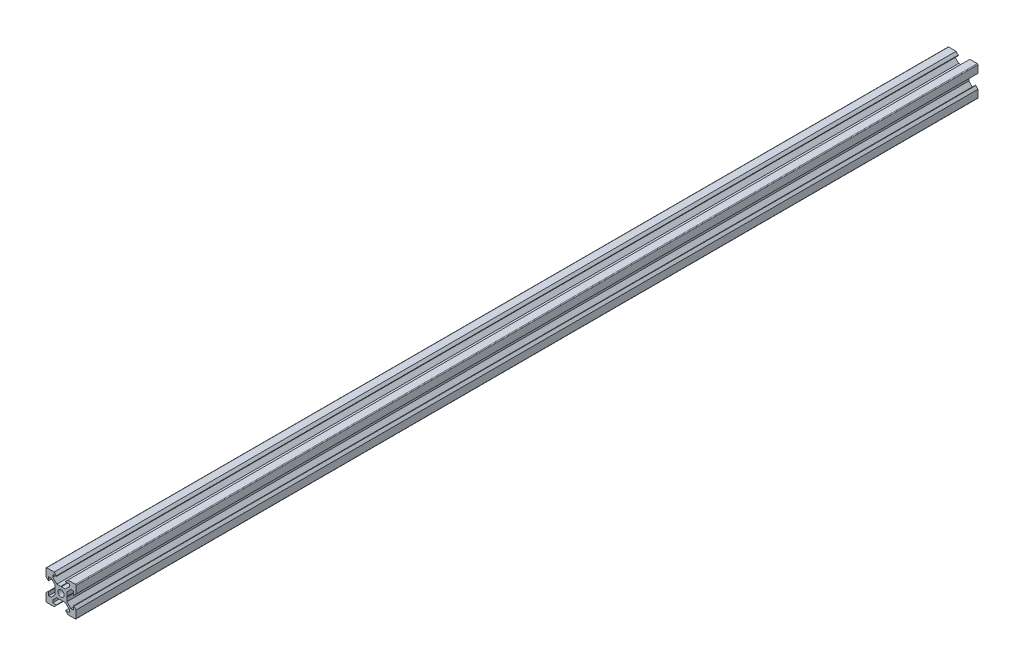
SolidWorks part; units mm, degrees
ref_plane "Plan de face" through (0, 0, 0) normal (0, 0, 1) x (1, 0, 0)
ref_plane "Plan de dessus" through (0, 0, 0) normal (0, 1, 0) x (1, 0, 0)
ref_plane "Plan de droite" through (0, 0, 0) normal (1, 0, 0) x (0, 0, -1)
ref_axis "Axe" through (0, 0, -13.782) along (0, 0, 1)
sketch "Esquisse1" plane through (0, 0, 0) normal (0, 0, 1) x (1, 0, 0)
  line L0 (0, 22.8977) -> (0, -22.8977) construction
  line L1 (-33.6074, 0) -> (33.6074, 0) construction
  line L2 (0, 0) -> (-22.2114, 22.2114) construction
  line L3 (-9.5, 10) -> (-4.58, 10)
  line L4 (-4.58, 10) -> (-3.125, 8.545)
  line L5 (-3.125, 8.545) -> (-3.125, 8.2)
  line L6 (-3.125, 8.2) -> (-5.5, 8.2)
  line L7 (-2.8393, 3.9) -> (-5.5, 6.5607)
  line L8 (-2.8393, 3.9) -> (-0.21, 3.9)
  line L9 (-5.5, 6.5607) -> (-5.5, 8.2)
  line L10 (0, 3.69) -> (0, 2.1)
  line L11 (-3.9, 2.8393) -> (-6.5607, 5.5)
  line L12 (-8.545, 3.125) -> (-8.2, 3.125)
  line L13 (-8.2, 3.125) -> (-8.2, 5.5)
  line L14 (-6.5607, 5.5) -> (-8.2, 5.5)
  line L15 (-10, 4.58) -> (-8.545, 3.125)
  line L16 (-10, 9.5) -> (-10, 4.58)
  line L17 (-0.21, 3.9) -> (0, 3.69)
  line L18 (-3.9, 2.8393) -> (-3.9, 0.21)
  line L19 (-3.69, 0) -> (-2.1, 0)
  line L20 (-3.9, 0.21) -> (-3.69, 0)
  arc A0 (-2.1, 0) -> (0, 2.1) centre (0, 0) cw
  arc A1 (-9.5, 10) -> (-10, 9.5) centre (-9.5, 9.5) ccw
  point P4 (0, 0)
  point P7 (0, 0)
  point P30 (-10, 10)
  dimension "D5" = 11
  dimension "D2" = 2.1
  dimension "D3" = 6.25
  dimension "D10" = 0.5
  dimension "D4" = 9.16
  dimension "D6" = 1.5
  dimension "D7" = 1.8
  dimension "D8" = 4.3
  dimension "D9" = 20
  dimension "D11" = 0.42
extrude "Boss.-Extru.1" add sketch "Esquisse1" along normal blind 600
sketch "Esquisse3" plane through (0, 0, 600) normal (0, 0, 1) x (1, 0, 0)
  line L0 (0, 0) -> (-9.8536, 9.8536) construction
  line L1 (-8.2, 8.2) -> (-8.2, 6.57)
  line L2 (-8.2, 6.57) -> (-7.54, 6.57)
  line L3 (-7.54, 6.57) -> (-6.57, 7.54)
  line L4 (-8.2, 3.125) -> (-8.2, 5.5) construction
  line L5 (-6.57, 8.2) -> (-6.57, 7.54)
  line L6 (-8.2, 8.2) -> (-6.57, 8.2)
  line L7 (-5.5, 6.5607) -> (-5.5, 8.2) construction
  arc A0 (-9.5, 10) -> (-10, 9.5) centre (-9.5, 9.5) ccw construction
  point P13 (-7.055, 7.055)
  point P14 (-6.57, 7.87)
  dimension "D1" = 1.07
extrude "Enlèv. mat.-Extru.1" [suppressed] cut sketch "Esquisse3" against normal through all
pattern_circular "Répétition circulaire1" count 4 every 90 about axis through (0, 0, -13.782) along (0, 0, 1) of "Boss.-Extru.1", "Enlèv. mat.-Extru.1"
